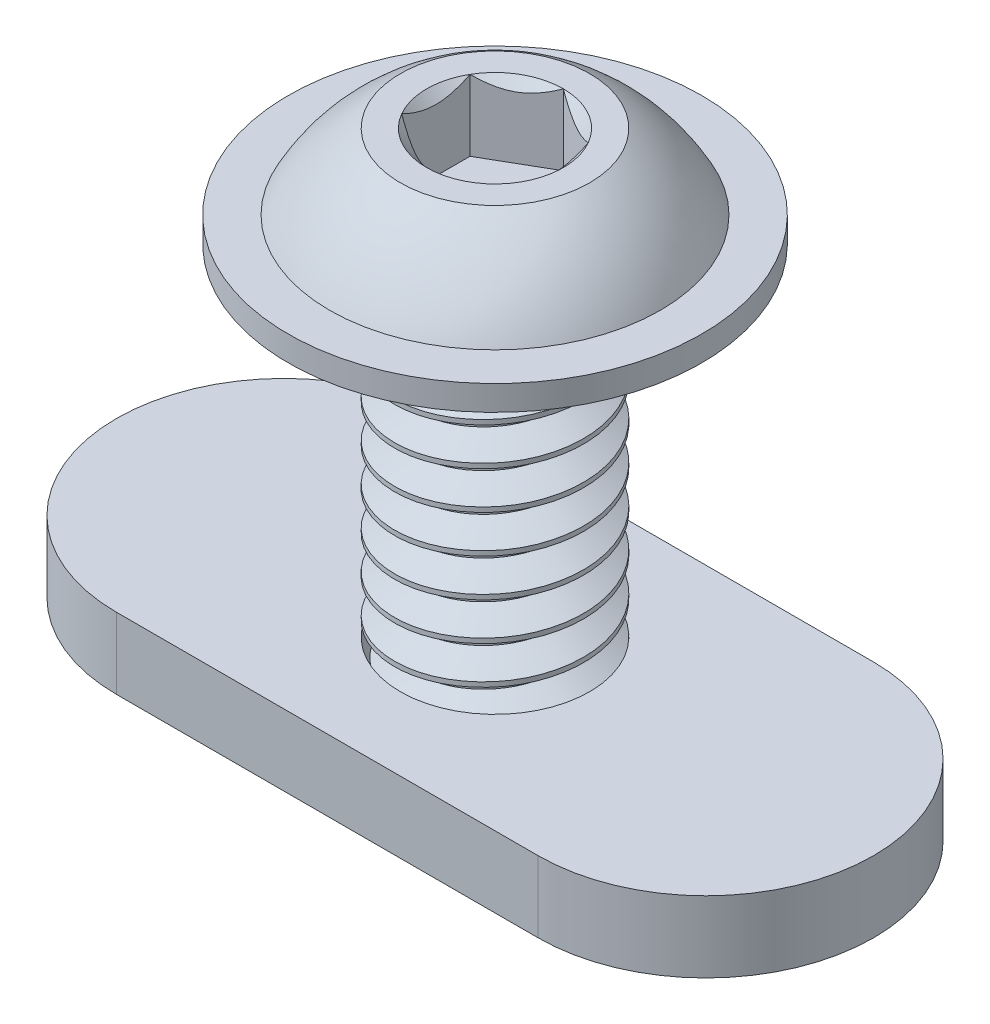
SolidWorks part; units mm, degrees
ref_plane "Front Plane" through (0, 0, 0) normal (0, 0, 1) x (1, 0, 0)
ref_plane "Top Plane" through (0, 0, 0) normal (0, 1, 0) x (1, 0, 0)
ref_plane "Right Plane" through (0, 0, 0) normal (1, 0, 0) x (0, 0, -1)
sketch "Sketch1" plane through (0, 0, 0) normal (0, 1, 0) x (1, 0, 0)
  circle A0 centre (0, 0) radius 3.175
  point P3 (-3.175, 0)
  point P4 (3.175, 0)
  dimension "D1" = 6.35
extrude "Boss-Extrude1" add sketch "Sketch1" against normal blind 12.7
sketch "Sketch2" plane through (0, -12.7, 0) normal (0, -1, 0) x (1, 0, 0)
  circle A1 centre (0, 0) radius 3.175
  circle A2 centre (0, 0) radius 3.175
  point P0 (0, -3.175)
  dimension "D1" = 0
curve "Helix/Spiral1" pitch 1.27 height 13.97 turns 11
sketch "Sketch3" plane through (0, 0, 0) normal (1, 0, 0) x (0, 0, -1)
  line L0 (3.3125, -12.6206) -> (2.2126, -13.2556) construction
  line L1 (2.2126, -13.2556) -> (3.3125, -13.8906) construction
  line L2 (3.3125, -13.8906) -> (3.3125, -12.6206) construction
  line L3 (2.3501, -13.1762) -> (2.3501, -13.335) construction
  line L4 (3.175, -12.7) -> (3.175, -13.8112) construction
  line L5 (2.2126, -13.2556) -> (2.3501, -13.2556) construction
  line L6 (3.175, -13.2556) -> (3.3125, -13.2556) construction
  line L8 (2.2126, -13.2556) -> (-3.175, -13.2556) construction
  line L9 (2.3501, -13.1762) -> (3.2437, -12.6603)
  line L10 (2.3501, -13.1762) -> (2.3501, -13.335)
  line L11 (2.3501, -13.335) -> (3.2437, -13.8509)
  line L12 (3.2437, -13.8509) -> (3.2437, -12.6603)
  line L14 (-3.175, -13.2556) -> (-3.175, -11.9856) construction
  line L15 (-3.175, -11.9856) -> (-3.175, -10.7156) construction
  line L16 (-3.175, -10.7156) -> (-3.175, -9.4456) construction
  line L17 (-3.175, -9.4456) -> (-3.175, -8.1756) construction
  line L18 (-3.175, 0) -> (-3.175, -12.7) construction
  point P15 (3.2437, -13.2556)
  dimension "D1" = 1.27
  dimension "D2" = 0.1588
sweep "Cut-Sweep1" cut profiles "Sketch3" path "Helix/Spiral1" align with end faces yes
sketch "Sketch4" plane through (0, -12.7, 0) normal (0, -1, 0) x (1, 0, 0)
  circle A0 centre (0, 0) radius 2.2126
extrude "Cut-Extrude1" cut sketch "Sketch4" against normal blind 1.27 draft 45 flip side to cut
sketch "Sketch5" plane through (0, 0, 0) normal (0, 0, 1) x (1, 0, 0)
  line L0 (0, 0) -> (0, 3.3528)
  line L1 (-6.9342, 0) -> (0, 0)
  line L2 (0, 3.3528) -> (-3.175, 3.3528)
  line L3 (-5.5499, 0.8382) -> (-6.9342, 0.8382)
  line L4 (-6.9342, 0.8382) -> (-6.9342, 0)
  line L5 (0, 0) -> (0, -12.7) construction
  arc A0 (-3.175, 3.3528) -> (-5.5499, 0.8382) centre (0, -2.0246) ccw
  dimension "D1" = 3.3528
  dimension "D2" = 0.8382
  dimension "D3" = 13.8684
  dimension "D4" = 11.0998
revolve "Revolve1" add sketch "Sketch5" angle 360 mid plane about L0
sketch "Sketch6" plane through (0, 3.3528, 0) normal (0, 1, 0) x (1, 0, 0)
  line L1 (0, 2.2914) -> (-1.9844, 1.1457)
  line L2 (-1.9844, 1.1457) -> (-1.9844, -1.1457)
  line L3 (-1.9844, -1.1457) -> (0, -2.2914)
  line L4 (0, -2.2914) -> (1.9844, -1.1457)
  line L5 (1.9844, -1.1457) -> (1.9844, 1.1457)
  line L6 (1.9844, 1.1457) -> (0, 2.2914)
  circle A0 centre (0, 0) radius 1.9844 construction
  dimension "D1" = 3.9688
extrude "Cut-Extrude2" cut sketch "Sketch6" against normal blind 2.3813
sketch "Sketch7" plane through (0, 3.3528, 0) normal (0, 1, 0) x (1, 0, 0)
  circle A0 centre (0, 0) radius 2.2914
extrude "Cut-Extrude3" cut sketch "Sketch7" against normal blind 2.3813 draft 45
sketch "Sketch8" plane through (0, 0, 0) normal (0, 1, 0) x (1, 0, 0)
  line L0 (-7.0739, 0) -> (7.0739, 0) construction
  line L1 (-7.0739, 5.6261) -> (7.0739, 5.6261)
  line L2 (-7.0739, -5.6261) -> (7.0739, -5.6261)
  line L4 (-12.7, 5.6261) -> (12.7, 5.6261) construction
  line L5 (-12.7, 5.6261) -> (-12.7, -5.6261) construction
  line L6 (-12.7, -5.6261) -> (12.7, -5.6261) construction
  line L7 (12.7, 5.6261) -> (12.7, -5.6261) construction
  arc A0 (-7.0739, 5.6261) -> (-7.0739, -5.6261) centre (-7.0739, 0) ccw
  arc A1 (7.0739, -5.6261) -> (7.0739, 5.6261) centre (7.0739, 0) ccw
  circle A3 centre (0, 0) radius 3.175
  circle A4 centre (0, 0) radius 3.175
  point P2 (0, 0)
  dimension "D2" = 25.4
  dimension "D3" = 11.2522
  dimension "D1" = 0
extrude "Boss-Extrude2" add sketch "Sketch8" against normal blind 2.3876 from offset 11.43 separate body offset against normal yes
sketch "Sketch9" plane through (0, -13.8176, 0) normal (0, -1, 0) x (1, 0, 0)
  circle A1 centre (0, 0) radius 3.175 construction
  circle A2 centre (0, 0) radius 3.175
  circle A3 centre (0, 0) radius 3.5687
  dimension "D1" = 7.1374
extrude "Boss-Extrude3" add sketch "Sketch9" along normal blind 0.762
sketch "SketchZ" plane through (0, 0, 0) normal (0, 0, 1) x (1, 0, 0)
  line L0 (3.175, -12.9381) -> (3.175, -11.6681) construction
  line L2 (0, -13.2556) -> (0, -11.9856) construction
  line L4 (3.175, -12.9381) -> (0, -12.9381) construction
  line L5 (0, -9.4456) -> (0, -8.1756) construction
  line L6 (0, -12.6206) -> (0, -13.2556) construction
equation "\"D3@Helix/Spiral1\" = \"D4@Helix/Spiral1\" + \"D1@Boss-Extrude1\""
equation "\"D1@Sketch3\" = \"D4@Helix/Spiral1\""
equation "\"D2@Sketch3\" = \"D1@Sketch3\" / 8"
equation "\"D1@Cut-Extrude1\" = \"D4@Helix/Spiral1\""
equation "\"D1@Cut-Extrude2\" = \"D1@Sketch6\" * 3/5"
equation "\"D1@Cut-Extrude3\" = \"D1@Cut-Extrude2\""
equation "\"D2@Sketch5\" = \"D1@Sketch5\" * 1/4"
